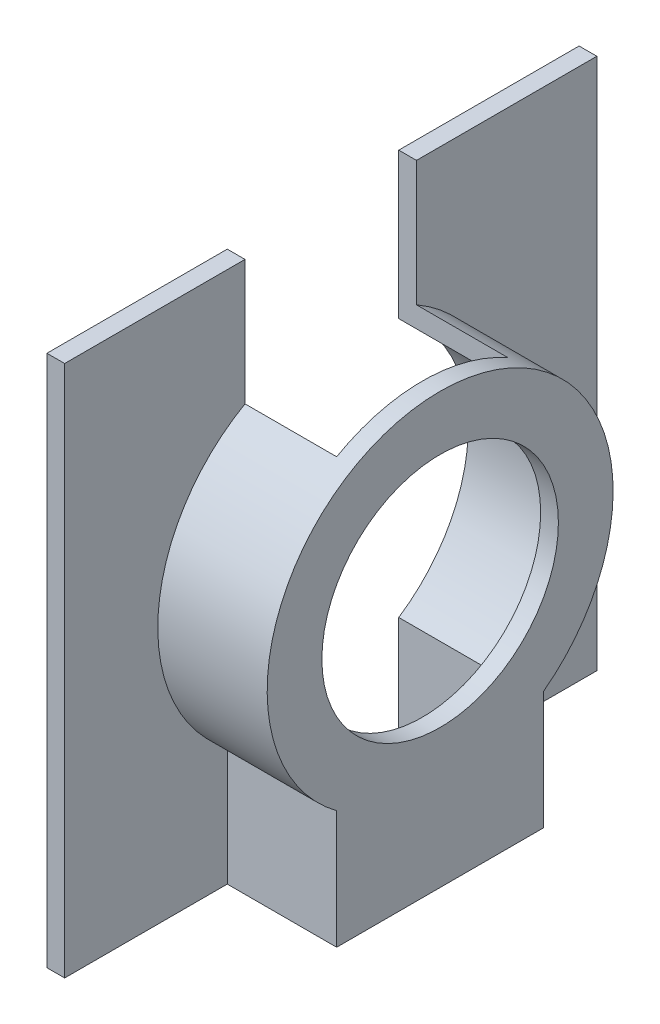
SolidWorks part; units mm, degrees
ref_plane "Front Plane" through (0, 0, 0) normal (0, 0, 1) x (1, 0, 0)
ref_plane "Top Plane" through (0, 0, 0) normal (0, 1, 0) x (1, 0, 0)
ref_plane "Right Plane" through (0, 0, 0) normal (1, 0, 0) x (0, 0, -1)
sketch "Sketch2" plane through (0, 0, 0) normal (1, 0, 0) x (0, 0, -1)
  line L1 (-9, -9) -> (9, -9)
  line L2 (-9, -9) -> (-9, 9)
  line L3 (-9, 9) -> (9, 9)
  line L4 (9, -9) -> (9, 9)
  line L5 (-9, -9) -> (9, 9) construction
  line L6 (-9, 9) -> (9, -9) construction
  point P0 (0, 0)
  dimension "D1" = 18
  dimension "D2" = 18
extrude "Boss-Extrude1" add sketch "Sketch2" along normal blind 4.3
sketch "Sketch4" plane through (4.3, 0, 0) normal (1, 0, 0) x (0, 0, -1)
  line L0 (-9, 0) -> (9, 0) construction
  line L1 (-9, 9) -> (-9, -9) construction
  line L2 (9, -9) -> (9, 9) construction
  line L3 (0, 9) -> (0, -9) construction
  line L4 (9, 9) -> (-9, 9) construction
  line L5 (-9, -9) -> (9, -9) construction
  line L7 (-3.5, -9) -> (3.5, -9)
  line L8 (-3.5, -9) -> (-3.5, -5)
  line L10 (3.5, -9) -> (3.5, -5)
  line L11 (-3.5, -9) -> (0, -6.1625) construction
  line L12 (0, -6.1625) -> (3.5, -9) construction
  arc A0 (3.5, -5) -> (-3.5, -5) centre (0, -0.3125) ccw
  point P14 (0, -6.1625)
  dimension "D1" = 11.7
  dimension "D2" = 7
  dimension "D3" = 4
extrude "Boss-Extrude2" add sketch "Sketch4" along normal blind 3.7
shell "Shell2" thickness 0.6 removed face at (0, 0, 0)
sketch "Sketch5" plane through (8, 0, 0) normal (1, 0, 0) x (0, 0, -1)
  line L0 (-5.85, -0.3125) -> (5.85, -0.3125) construction
  arc A0 (3.5, -5) -> (-3.5, -5) centre (0, -0.3125) ccw construction
  arc A1 (3.5, -5) -> (-3.5, -5) centre (0, -0.3125) ccw construction
  circle A2 centre (0, -0.3125) radius 4
  dimension "D1" = 8
extrude "Cut-Extrude1" cut sketch "Sketch5" against normal through all
ref_plane "Plane1" through (0, 5.5375, 0) normal (0, 1, 0) x (1, 0, 0)
sketch "Sketch6" plane through (0, -9, 0) normal (0, 1, 0) x (1, 0, 0)
  line L1 (0, 8.4) -> (0, -8.4)
  line L3 (3.7, -8.4) -> (3.7, -2.9)
  line L4 (3.7, -2.9) -> (7.4, -2.9)
  line L5 (7.4, -2.9) -> (7.4, 2.9)
  line L6 (7.4, 2.9) -> (3.7, 2.9)
  line L7 (3.7, 2.9) -> (3.7, 8.4)
  line L8 (0, 8.4) -> (0, 9)
  line L9 (0, 9) -> (3.7, 9)
  line L10 (4.3, 9) -> (0, 9) construction
  line L11 (3.7, 9) -> (3.7, 8.4)
  line L12 (0, -8.5743) -> (0, -9)
  line L13 (0, 9) -> (0, -9) construction
  line L14 (0, -9) -> (3.7, -9)
  line L15 (4.3, -9) -> (0, -9) construction
  line L16 (3.7, -9) -> (3.7, -8.4)
extrude "Cut-Extrude2" cut sketch "Sketch6" along normal through all and the other way through all
